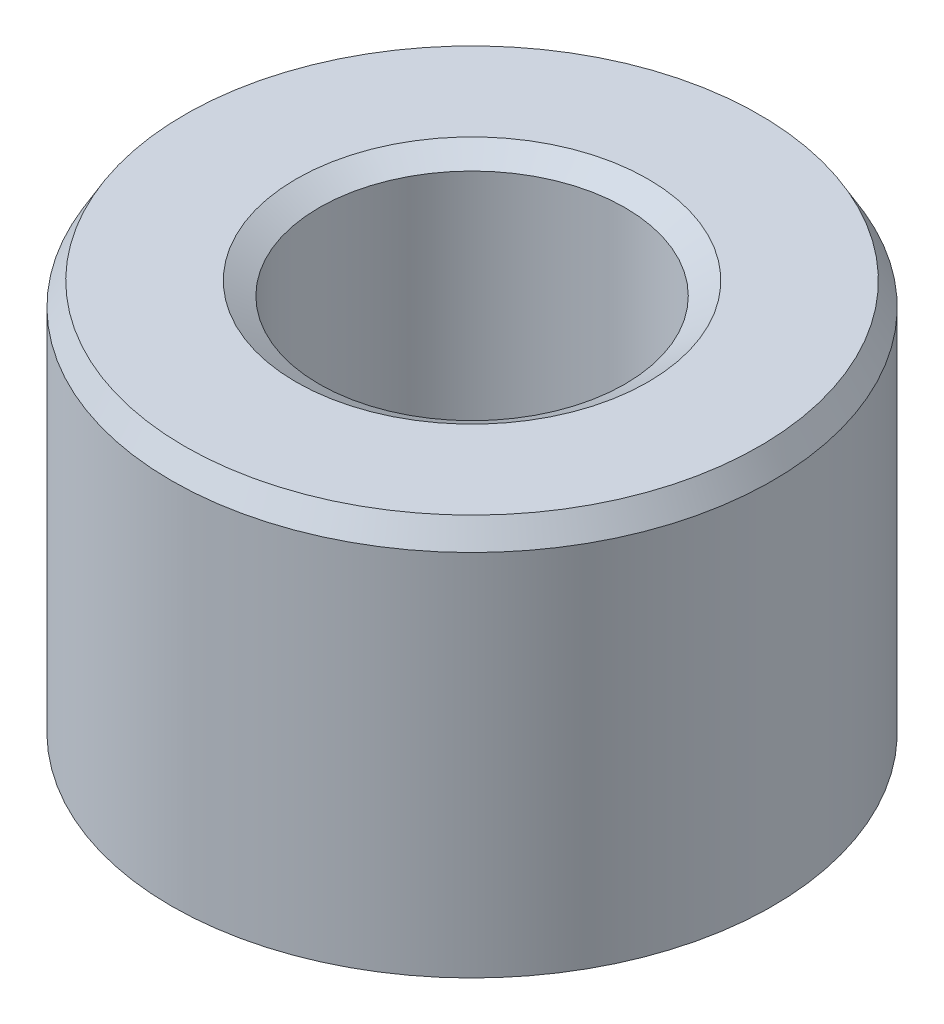
SolidWorks part; units mm, degrees
ref_plane "Front Plane" through (0, 0, 0) normal (0, 0, 1) x (1, 0, 0)
ref_plane "Top Plane" through (0, 0, 0) normal (0, 1, 0) x (1, 0, 0)
ref_plane "Right Plane" through (0, 0, 0) normal (1, 0, 0) x (0, 0, -1)
sketch "Sketch1" plane through (0, 0, 0) normal (0, 1, 0) x (1, 0, 0)
  circle A0 centre (0, 0) radius 45
  dimension "SLEEVE_OD" = 90
extrude "Boss-Extrude1" add sketch "Sketch1" along normal blind 60.588
sketch "Sketch2" plane through (0, 0, 0) normal (0, 1, 0) x (1, 0, 0)
  circle A0 centre (0, 0) radius 22.889
  dimension "BORE_D" = 45.7779
extrude "Cut-Extrude1" cut sketch "Sketch2" along normal through all
chamfer "Chamfer1" distance 3.4442 angle 30 4 edges at (0, 60.588, 22.889) (0, 0, 22.889) (0, 0, 45) (0, 60.588, 45) first distance on face at (0, 60.588, 22.889) first distance on face at (0, 0, 22.889) first distance on face at (0, 60.588, 45)
